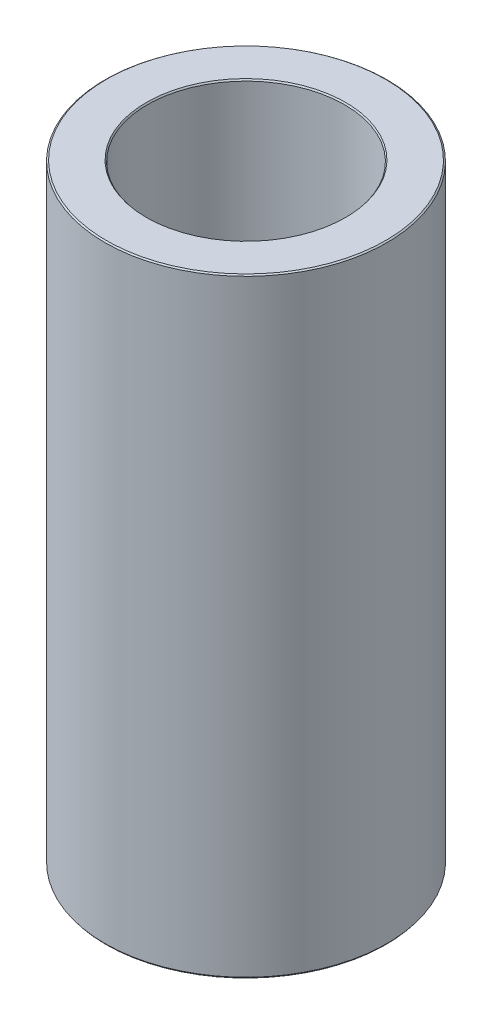
SolidWorks part; units mm, degrees
ref_plane "Front Plane" through (0, 0, 0) normal (0, 0, 1) x (1, 0, 0)
ref_plane "Top Plane" through (0, 0, 0) normal (0, 1, 0) x (1, 0, 0)
ref_plane "Right Plane" through (0, 0, 0) normal (1, 0, 0) x (0, 0, -1)
sketch "Sketch1" plane through (0, 0, 0) normal (0, 1, 0) x (1, 0, 0)
  circle A0 centre (0, 0) radius 42.5
  dimension "SLEEVE_OD" = 85
extrude "Boss-Extrude1" add sketch "Sketch1" along normal blind 183.6329
sketch "Sketch2" plane through (0, 0, 0) normal (0, 1, 0) x (1, 0, 0)
  circle A0 centre (0, 0) radius 29.7094
  dimension "BORE_D" = 59.4188
extrude "Cut-Extrude1" cut sketch "Sketch2" along normal through all
chamfer "Chamfer1" distance 0.3217 angle 53.25 4 edges at (0, 183.6329, 29.7094) (0, 0, 29.7094) (0, 0, 42.5) (0, 183.6329, 42.5) first distance on face at (0, 183.6329, 29.7094) first distance on face at (0, 0, 29.7094) first distance on face at (0, 183.6329, 42.5)
